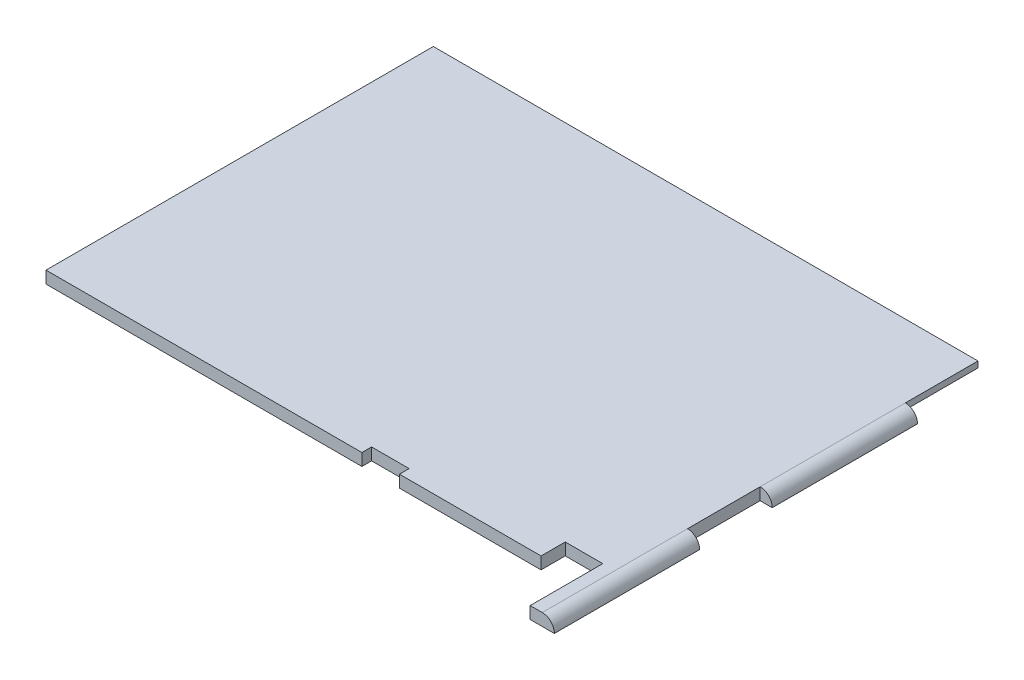
SolidWorks part; units mm, degrees
ref_plane "前基準面" through (0, 0, 0) normal (0, 0, 1) x (1, 0, 0)
ref_plane "上基準面" through (0, 0, 0) normal (0, 1, 0) x (1, 0, 0)
ref_plane "右基準面" through (0, 0, 0) normal (1, 0, 0) x (0, 0, -1)
sketch "草圖1" plane through (0, 0, 0) normal (0, 1, 0) x (1, 0, 0)
  line L0 (-36.2537, 43.5351) -> (203.7463, 43.5351)
  line L1 (203.7463, 43.5351) -> (203.7463, -286.4649)
  line L2 (198.7463, -286.4649) -> (198.7463, -256.4649)
  line L3 (198.7463, -256.4649) -> (183.2463, -256.4649)
  line L4 (183.2463, -256.4649) -> (183.2463, -266.4649)
  line L5 (183.2463, -266.4649) -> (124.7463, -266.4649)
  line L6 (124.7463, -266.4649) -> (124.7463, -262.4649)
  line L7 (124.7463, -262.4649) -> (109.2463, -262.4649)
  line L8 (109.2463, -262.4649) -> (109.2463, -266.4649)
  line L9 (109.2463, -266.4649) -> (-21.2537, -266.4649)
  line L10 (-21.2537, -266.4649) -> (-21.2537, 38.5351)
  line L11 (-21.2537, 38.5351) -> (-36.2537, 38.5351)
  line L12 (-36.2537, 38.5351) -> (-36.2537, 43.5351)
  line L13 (198.7463, -286.4649) -> (203.7463, -286.4649)
  line L15 (203.7463, -286.4649) -> (208.7463, -286.4649)
  line L16 (203.7463, -286.4649) -> (203.7463, -226.4649)
  line L17 (203.7463, -226.4649) -> (208.7463, -226.4649)
  line L18 (208.7463, -286.4649) -> (208.7463, -226.4649)
  line L19 (-36.2537, 43.5351) -> (-6.2537, 43.5351)
  line L20 (-36.2537, 43.5351) -> (-36.2537, 48.5351)
  line L21 (-36.2537, 48.5351) -> (-6.2537, 48.5351)
  line L22 (-6.2537, 43.5351) -> (-6.2537, 48.5351)
  line L23 (203.7463, 43.5351) -> (173.7463, 43.5351)
  line L24 (203.7463, 43.5351) -> (203.7463, 48.5351)
  line L25 (203.7463, 48.5351) -> (173.7463, 48.5351)
  line L26 (173.7463, 43.5351) -> (173.7463, 48.5351)
  line L27 (203.7463, 43.5351) -> (208.7463, 43.5351)
  line L28 (203.7463, 43.5351) -> (203.7463, -16.4649)
  line L29 (203.7463, -16.4649) -> (208.7463, -16.4649)
  line L30 (208.7463, 43.5351) -> (208.7463, -16.4649)
  line L31 (83.7463, 43.5351) -> (98.7463, 43.5351)
  line L32 (83.7463, 43.5351) -> (83.7463, 48.5351)
  line L33 (83.7463, 48.5351) -> (98.7463, 48.5351)
  line L34 (98.7463, 43.5351) -> (98.7463, 48.5351)
  line L35 (83.7463, 43.5351) -> (68.7463, 43.5351)
  line L36 (83.7463, 43.5351) -> (83.7463, 48.5351)
  line L37 (83.7463, 48.5351) -> (68.7463, 48.5351)
  line L38 (68.7463, 43.5351) -> (68.7463, 48.5351)
  line L39 (203.7463, -46.4649) -> (208.7463, -46.4649)
  line L40 (203.7463, -46.4649) -> (203.7463, -106.4649)
  line L41 (203.7463, -106.4649) -> (208.7463, -106.4649)
  line L42 (208.7463, -46.4649) -> (208.7463, -106.4649)
  line L43 (203.7463, -136.4649) -> (208.7463, -136.4649)
  line L44 (203.7463, -136.4649) -> (203.7463, -196.4649)
  line L45 (203.7463, -196.4649) -> (208.7463, -196.4649)
  line L46 (208.7463, -136.4649) -> (208.7463, -196.4649)
  dimension "D3" = 5
  dimension "D1" = 240
  dimension "D2" = 330
  dimension "D4" = 15
  dimension "D5" = 130.5
  dimension "D6" = 4
  dimension "D7" = 4
  dimension "D8" = 15.5
  dimension "D9" = 58.5
  dimension "D10" = 10
  dimension "D11" = 15.5
  dimension "D12" = 30
  dimension "D13" = 5
  dimension "D14" = 60
  dimension "D15" = 5
  dimension "D16" = 5
  dimension "D17" = 30
  dimension "D18" = 5
  dimension "D19" = 30
  dimension "D20" = 60
  dimension "D21" = 5
  dimension "D22" = 5
  dimension "D23" = 15
  dimension "D24" = 5
  dimension "D25" = 15
  dimension "D26" = 60
  dimension "D27" = 5
  dimension "D28" = 30
  dimension "D29" = 60
  dimension "D30" = 5
  dimension "D31" = 30
  dimension "D32" = 30
extrude "填料-伸長1" add sketch "草圖1" along normal blind 5 contours L2 L13 L1 L0 L12 L11 L10 L9 L8 L7 L6 L5 L4 L3 | L15 L18 L17 L1 | L30 L27 L1 L29 | L26 L0 L24 L25 | L0 L22 L21 L20 | L32 L33 L34 L31 | L36 L37 L38 L35 | L46 L45 L44 L43 | L42 L41 L40 L39 region at (-21.2537, 0, -46.0351) region at (91.0303, 0, 111.0679) region at (188.7463, 0, -46.0351) region at (206.2463, 0, -13.5351) region at (206.2463, 0, 256.4649)
fillet "圓角1" radius 5 4 edges at (208.7463, 5, -13.5351) (208.7463, 5, 76.4649) (208.7463, 5, 166.4649) (208.7463, 5, 256.4649)
sketch "草圖2" plane through (0, 5, 0) normal (0, 1, 0) x (1, 0, 0)
  line L1 (-36.2537, 48.5351) -> (208.7463, 48.5351)
  line L2 (-36.2537, 48.5351) -> (-36.2537, -106.4649)
  line L3 (-36.2537, -106.4649) -> (208.7463, -106.4649)
  line L4 (208.7463, 48.5351) -> (208.7463, -106.4649)
extrude "除料-伸長1" cut sketch "草圖2" against normal blind 5
sketch "草圖3" plane through (203.7463, 0, 0) normal (1, 0, 0) x (0, 0, -1)
  line L1 (-106.4649, 0) -> (-136.4649, 0)
  line L2 (-106.4649, 0) -> (-106.4649, 2.5)
  line L3 (-106.4649, 2.5) -> (-136.4649, 2.5)
  line L4 (-136.4649, 0) -> (-136.4649, 2.5)
  line L5 (-136.4649, 0) -> (-136.4649, 5) construction
  dimension "D1" = 2.5
  dimension "D2" = 30
extrude "除料-伸長2" cut sketch "草圖3" against normal through all
